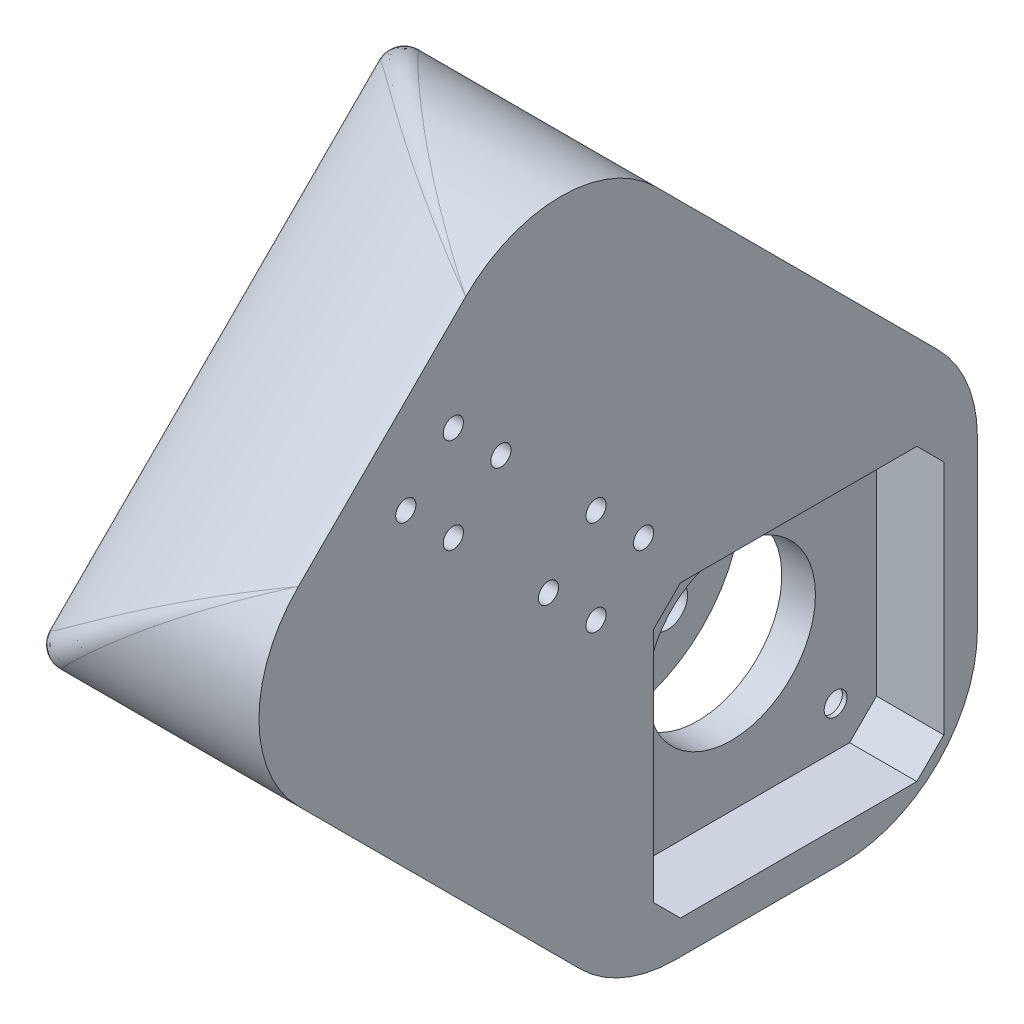
SolidWorks part; units mm, degrees
ref_plane "Front Plane" through (0, 0, 0) normal (0, 0, 1) x (1, 0, 0)
ref_plane "Top Plane" through (0, 0, 0) normal (0, 1, 0) x (1, 0, 0)
ref_plane "Right Plane" through (0, 0, 0) normal (1, 0, 0) x (0, 0, -1)
sketch "Sketch1" plane through (0, 0, 0) normal (1, 0, 0) x (0, 0, -1)
  line L0 (-11.075, 42.075) -> (42.075, 42.075) construction
  line L1 (0, 0) -> (31, 0) construction
  line L2 (0, 0) -> (0, 31) construction
  line L3 (0, 31) -> (31, 31) construction
  line L4 (31, 0) -> (31, 31) construction
  line L5 (-6.075, -6.075) -> (37.075, -6.075)
  line L6 (-6.075, -6.075) -> (-6.075, 37.075)
  line L7 (-6.075, 37.075) -> (37.075, 37.075)
  line L8 (37.075, -6.075) -> (37.075, 37.075)
  line L9 (42.075, -11.075) -> (42.075, 42.075)
  line L10 (-11.075, -11.075) -> (42.075, -11.075)
  line L11 (-11.075, -11.075) -> (-11.075, 42.075) construction
  line L12 (-11.075, -11.075) -> (-37.65, 15.5)
  line L13 (-37.65, 15.5) -> (-11.075, 42.075)
  line L14 (-11.075, 42.075) -> (15.5, 68.65)
  line L15 (15.5, 68.65) -> (42.075, 42.075)
  point P9 (31, 15.5)
  point P10 (37.075, 15.5)
  point P11 (15.5, -6.075)
  point P12 (15.5, 0)
  dimension "D2" = 31
  dimension "D3" = 43.15
  dimension "D5" = 5
extrude "Boss-Extrude1" add sketch "Sketch1" along normal blind 5 contours L5 L8 L7 L6 | L11 L10 L9 L0 L8 L5 L6 L7 region at (0, 15.5, -15.5) region at (0, -9.9475, -15.5)
extrude "Boss-Extrude2" add sketch "Sketch1<3>" along normal blind 10 from surface starting at face at (5, 20.815, -10.185)
sketch "Sketch1<3>" plane through (0, 0, 0) normal (1, 0, 0) x (0, 0, -1) same geometry as "Sketch1"
sketch "Sketch6" plane through (0, 0, 0) normal (-1, 0, 0) x (0, 0, 1)
  line L2 (11.075, -11.075) -> (-42.075, -11.075) construction
  line L3 (-42.075, -11.075) -> (-42.075, 42.075) construction
  circle A0 centre (-15.5, 15.5) radius 12.5
  point P11 (-15.5, -11.075)
  point P15 (-42.075, 15.5)
  dimension "D1" = 25
extrude "Cut-Extrude1" cut sketch "Sketch6" against normal blind 10
chamfer "Chamfer1" distance 4 angle 45 4 edges at (10, -6.075, -37.075) (10, 37.075, -37.075) (10, 37.075, 6.075) (10, -6.075, 6.075)
sketch "Sketch8" plane through (0, -11.075, 11.075) normal (0, -0.7071, 0.7071) x (1, 0, 0)
  line L0 (15, 37.5827) -> (15, 87.5827)
  line L5 (15, 37.5827) -> (0, 37.5827)
  line L6 (-33, 37.5827) -> (-20, 37.5827)
  line L7 (-33, 87.5827) -> (-33, 37.5827)
  line L8 (15, 87.5827) -> (-33, 87.5827)
  line L9 (15, 37.5827) -> (15, 0) construction
  line L10 (15, 37.5827) -> (0, 37.5827) construction
  line L11 (-20, 37.5827) -> (-20, 47.5827)
  line L12 (0, 37.5827) -> (0, 47.5827)
  arc A4 (0, 47.5827) -> (-20, 47.5827) centre (-10, 47.5827) ccw
  dimension "D2" = 13
  dimension "D1" = 48
  dimension "D4" = 10
  dimension "D3" = 50
extrude "Boss-Extrude10" add sketch "Sketch8" against normal up to surface (75.1655 mm away) up to face at (7.5, 55.3625, -28.7875)
extrude "Boss-Extrude11" add sketch "Sketch1<5>" along normal blind 13 from surface contours L15 L14 L13 L12 L10 L9 L8 L5 L6 L7 | L5 L8 L7 L6 region at (0, 15.5, -15.5) region at (0, -9.9475, -15.5) starting at face at (-33, 59.7527, 28.7527)
sketch "Sketch1<5>" plane through (0, 0, 0) normal (1, 0, 0) x (0, 0, -1) same geometry as "Sketch1"
fillet "Fillet1" radius 20 8 edges at (-26.5, -11.075, -42.075) (7.5, -11.075, -42.075) (-26.5, -11.075, 11.075) (7.5, -11.075, 11.075) (-26.5, 42.075, -42.075) (7.5, 42.075, -42.075) (-9, 50.8553, 73.0053) (-9, 104.0053, 19.8553)
sketch "Sketch11" plane through (-20, 0, 0) normal (1, 0, 0) x (0, 0, -1)
  circle A0 centre (15.5, 15.5) radius 11
  circle A1 centre (15.5, 15.5) radius 12.5 construction
  circle A2 centre (15.5, 15.5) radius 4.5
  dimension "D1" = 22
  dimension "D2" = 9
extrude "Cut-Extrude2" cut sketch "Sketch11" against normal blind 7
extrude "Cut-Extrude3" cut sketch "Sketch11<2>" against normal through all contours A2 region at (-20, 15.5, -15.5)
sketch "Sketch11<2>" plane through (-20, 0, 0) normal (1, 0, 0) x (0, 0, -1) same geometry as "Sketch11"
hole_wizard "CBORE for M3 Hex Head Machine Screw2" positions "Sketch4" profile "Sketch5" counterbore size "M3" standard "ANSI Metric" end condition through all
sketch "Sketch4" plane through (0, 0, 0) normal (-1, 0, 0) x (0, 0, 1)
  line L1 (0, 0) -> (-31, 0) construction
  line L2 (0, 0) -> (0, 31) construction
  line L3 (0, 31) -> (-31, 31) construction
  line L4 (-31, 0) -> (-31, 31) construction
  point P0 (-31, 31)
  point P2 (0, 0)
  point P5 (0, 31)
  point P7 (-31, 0)
  dimension "D1" = 31
sketch "Sketch5" plane through (0, 31, -31) normal (0, 1, 0) x (0, 0, 1)
  line L0 (0, 0) -> (0, 15)
  line L1 (0, 15) -> (1.7, 15)
  line L3 (1.7, 15) -> (1.7, 4.3)
  line L4 (1.7, 4.3) -> (3, 4.3)
  line L5 (3, 4.3) -> (3, 0)
  line L7 (3, 0) -> (0, 0)
  line L11 (0, -6.35) -> (0, 107.95) construction
  dimension "Thru Hole Dia." = 3.4
  dimension "Thru Hole Depth" = 15
  dimension "C'Bore Dia." = 6
  dimension "C'Bore Depth" = 4.3
sketch "Sketch13" plane through (-33, 0, 0) normal (-1, 0, 0) x (0, 0, 1)
  circle A0 centre (0, 31) radius 3
  circle A1 centre (0, 0) radius 3
  circle A2 centre (-31, 0) radius 3
  circle A3 centre (-31, 31) radius 3
  dimension "D1" = 6
extrude "Cut-Extrude4" cut sketch "Sketch13" against normal up to surface (13 mm away) up to face at (-20, 15.5, -26.5)
hole_wizard "Ø3.0mm Dowel Hole1" positions "Sketch14" profile "Sketch15" hole size "Ø3.0" standard "DIN"
sketch "Sketch14" plane through (15, 0, 0) normal (1, 0, 0) x (0, 0, -1)
  line L1 (-42.8948, 66.8237) -> (-35.8237, 73.8948) construction
  line L2 (-35.8237, 73.8948) -> (-28.7527, 66.8237) construction
  line L3 (-28.7527, 66.8237) -> (-35.8237, 59.7527) construction
  line L4 (-35.8237, 59.7527) -> (-42.8948, 66.8237) construction
  line L6 (-21.6816, 45.6105) -> (-14.6105, 52.6816) construction
  line L7 (-14.6105, 52.6816) -> (-7.5395, 45.6105) construction
  line L8 (-7.5395, 45.6105) -> (-14.6105, 38.5395) construction
  line L9 (-14.6105, 38.5395) -> (-21.6816, 45.6105) construction
  line L11 (-32.2882, 63.2882) -> (-18.1461, 49.1461) construction
  line L13 (-33.9975, 89.8632) -> (-58.8632, 64.9975) construction
  line L14 (-46.4303, 77.4303) -> (-39.3593, 70.3593) construction
  point P0 (-35.8237, 73.8948)
  point P2 (-42.8948, 66.8237)
  point P4 (-35.8237, 59.7527)
  point P6 (-28.7527, 66.8237)
  point P8 (-14.6105, 52.6816)
  point P10 (-21.6816, 45.6105)
  point P12 (-14.6105, 38.5395)
  point P14 (-7.5395, 45.6105)
  point P159 (-18.1461, 49.1461)
  point P178 (-39.3593, 70.3593)
  dimension "D1" = 10
  dimension "D2" = 20
  dimension "D3" = 10
sketch "Sketch15" plane through (15, 73.8948, 35.8237) normal (0, 1, 0) x (0, 0, -1)
  line L0 (0, 0) -> (0, 7.9013)
  line L1 (0, 7.9013) -> (1.5, 7)
  line L2 (1.5, 7) -> (1.5, 0)
  line L5 (1.5, 0) -> (0, 0)
  line L10 (0, 7.9013) -> (-1.5, 7) construction
  line L11 (0, -6.35) -> (0, 107.95) construction
  dimension "Hole Dia." = 3
  dimension "Hole Depth" = 7
  dimension "Drill Angle" = 118
sketch "Sketch16" plane through (0, -11.075, 11.075) normal (0, -0.7071, 0.7071) x (1, 0, 0)
  line L0 (-33, 67.5827) -> (-33, 8.2843) construction
  line L1 (-33, 87.5827) -> (15, 87.5827) construction
  line L2 (-33, 39.5827) -> (-33, 87.5827)
  line L3 (-33, 87.5827) -> (15, 87.5827)
  arc A0 (-33, 39.5827) -> (15, 87.5827) centre (15, 39.5827) cw
extrude "Cut-Extrude5" cut sketch "Sketch16" against normal through all
fillet "Fillet2" radius 3 11 edges at (-6.5973, 95.6934, 20.9078) (-30.6913, 80.4639, -3.6861) (-33, 58.9985, -25.1515) (-33, 41.4444, -40.5526) (-33, 21.3579, -42.075) (-33, -5.2171, -36.2171) (-33, -11.075, -9.6421) (-33, -9.5526, 10.4444) (-33, 5.8485, 27.9985) (-30.6913, 27.3139, 49.4639) (-6.5973, 51.9078, 64.6934)
